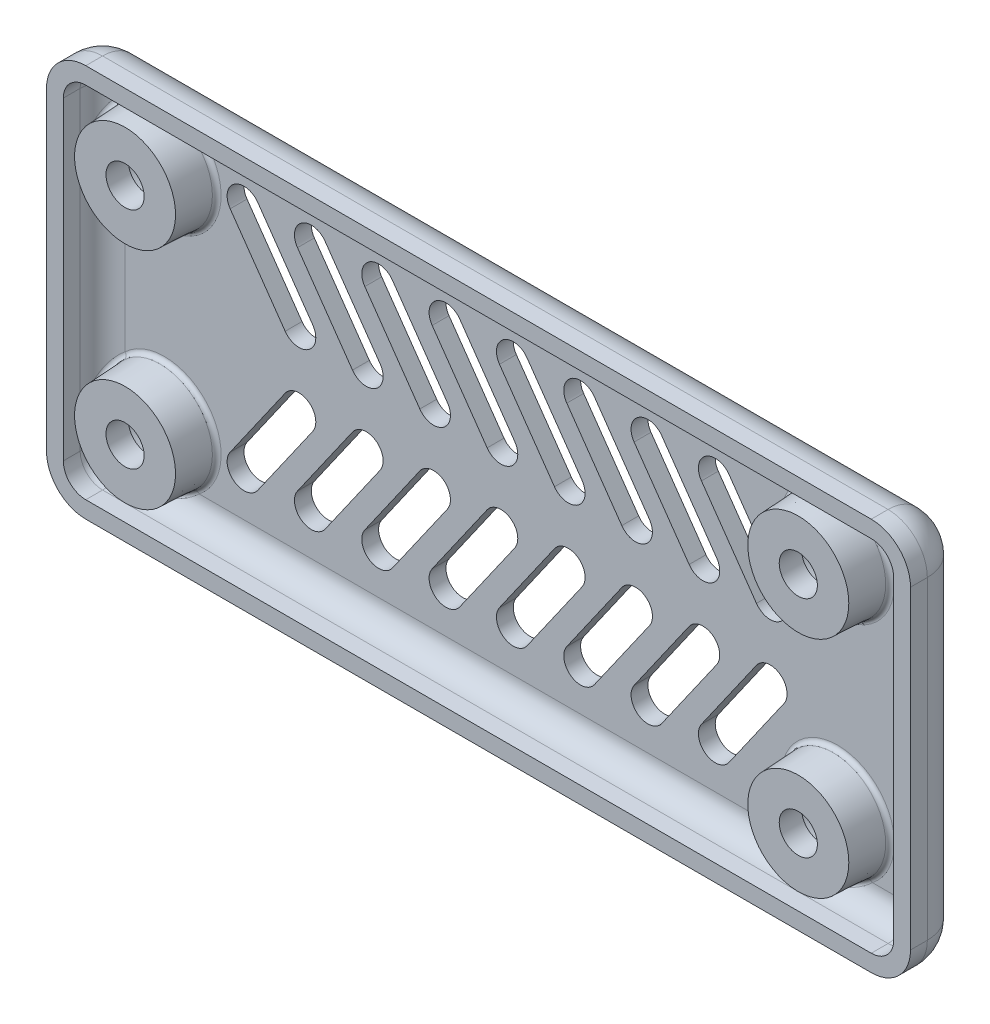
SolidWorks part; units mm, degrees
ref_plane "Płaszczyzna przednia" through (0, 0, 0) normal (0, 0, 1) x (1, 0, 0)
ref_plane "Płaszczyzna górna" through (0, 0, 0) normal (0, 1, 0) x (1, 0, 0)
ref_plane "Płaszczyzna prawa" through (0, 0, 0) normal (1, 0, 0) x (0, 0, -1)
sketch "Szkic1" plane through (0, 0, 0) normal (0, 0, 1) x (1, 0, 0)
  line L0 (0, 0) -> (1.5, 0) construction
  line L1 (-37, 17.5) -> (40, 17.5)
  line L2 (-37, 17.5) -> (-37, -17.5)
  line L3 (-37, -17.5) -> (40, -17.5)
  line L4 (40, 17.5) -> (40, -17.5)
  line L5 (-37, 17.5) -> (40, -17.5) construction
  line L6 (-37, -17.5) -> (40, 17.5) construction
  dimension "D1" = 37
  dimension "D2" = 35
  dimension "D3" = 40
extrude "Dodanie-wyciągnięcie1" add sketch "Szkic1" along normal blind 5
fillet "Zaokrąglenie1" radius 3.5 8 edges at (1.5, 17.5, 0) (-37, 0, 0) (1.5, -17.5, 0) (40, 0, 0) (-37, -17.5, 2.5) (40, -17.5, 2.5) (40, 17.5, 2.5) (-37, 17.5, 2.5)
shell "Skorupa1" thickness 1.5
ref_plane "Płaszczyzna1" through (0, 0, 5) normal (0, 0, 1) x (1, 0, 0)
sketch "Szkic2" plane through (0, 0, 5) normal (0, 0, 1) x (1, 0, 0)
  line L1 (-30, 10) -> (30, 10) construction
  line L2 (-30, 10) -> (-30, -10) construction
  line L3 (-30, -10) -> (30, -10) construction
  line L4 (30, 10) -> (30, -10) construction
  line L5 (-30, 10) -> (30, -10) construction
  line L6 (-30, -10) -> (30, 10) construction
  circle A0 centre (-30, 10) radius 2.5 construction
  circle A5 centre (30, 10) radius 2.5 construction
  circle A6 centre (30, 10) radius 4.5
  circle A7 centre (-30, 10) radius 4.5
  circle A8 centre (-30, -10) radius 2.5 construction
  circle A9 centre (30, -10) radius 2.5 construction
  circle A10 centre (-30, -10) radius 4.5
  circle A11 centre (30, -10) radius 4.5
  point P0 (0, 0)
  dimension "D3" = 5
  dimension "D4" = 2
  dimension "D1" = 20
  dimension "D2" = 60
extrude "Dodanie-wyciągnięcie2" add sketch "Szkic2" against normal up to surface (3.5 mm away) draft 3
fillet "Zaokrąglenie2" radius 0.4 12 edges at (30, -5.3166, 1.5) (29.5676, -14.6576, 1.6112) (30, 5.3166, 1.5) (30.4324, 14.6576, 1.6112) (-34.5958, -10.8079, 1.8269) (-26.4044, -6.9989, 1.5) (-33.0011, -13.5956, 1.5) (-30.4324, -14.6576, 1.6112) (-34.5958, 9.1921, 1.8269) (-26.4044, 6.9989, 1.5) (-33.0011, 13.5956, 1.5) (-29.5676, 14.6576, 1.6112)
hole_wizard "Pogłębienie walcowe pod M3 Śrubę z łbem stożkowym ściętym1" positions "Szkic 3D1" profile "Szkic3" counterbore size "M3" standard "ISO" end condition through all
sketch3d "Szkic 3D1"
  circle A0 centre (-30, -10, 5) radius 4.5 construction
  circle A1 centre (-30, 10, 5) radius 4.5 construction
  circle A2 centre (30, 10, 5) radius 4.5 construction
  circle A3 centre (30, -10, 5) radius 4.5 construction
  point P16 (-30, -10, 0)
  point P18 (30, -10, 0)
  point P20 (30, 10, 0)
  point P22 (-30, 10, 0)
  point P24 (0, 0, 0)
  point P27 (-30, -10, 9.5)
  point P30 (-30, 10, 9.5)
  point P31 (0, 0, 0)
  point P32 (0, 0, 0)
  point P35 (30, 10, 9.5)
  point P36 (0, 0, 0)
  point P39 (30, -10, 9.5)
  point P40 (0, 0, 0)
sketch "Szkic3" plane through (-30, -10, 0) normal (1, 0, 0) x (0, 1, 0)
  line L0 (0, 0) -> (0, 5)
  line L1 (0, 5) -> (1.7, 5)
  line L3 (1.7, 5) -> (1.7, 3)
  line L4 (1.7, 3) -> (3.5, 3)
  line L5 (3.5, 3) -> (3.5, 0)
  line L7 (3.5, 0) -> (0, 0)
  line L11 (0, -6.35) -> (0, 107.95) construction
  dimension "Średnica otworu na wylot" = 3.4
  dimension "Głębokość otworu na wylot" = 5
  dimension "Średnica pogłębienia walcowego" = 7
  dimension "Głębokość pogłębienia walcowego" = 3
sketch "Szkic4" plane through (-37, 0, 0) normal (-1, 0, 0) x (0, 0, 1)
  line L0 (5, 14) -> (5, -14) construction
  circle A0 centre (-3.7, -0.5) radius 5
  point P4 (0, 0)
  point P5 (0, 0)
  dimension "D1" = 10
  dimension "D2" = 8.7
  dimension "D3" = 0.5
extrude "Wytnij-wyciągnięcie1" [suppressed] cut sketch "Szkic4" against normal up to surface (1.5 mm away)
sketch "Szkic6" plane through (40, 0, 0) normal (1, 0, 0) x (0, 0, -1)
  line L0 (2, 0) -> (0, 0) construction
  line L1 (-5, -14) -> (-5, 14) construction
  circle A0 centre (2, 0) radius 4
  dimension "D1" = 8
  dimension "D2" = 7
extrude "Wytnij-wyciągnięcie2" [suppressed] cut sketch "Szkic6" against normal up to surface (1.5 mm away)
sketch "Szkic7" plane through (0, 0, 0) normal (0, 0, -1) x (-1, 0, 0)
  line L0 (0, 0) -> (-24, 0) construction
  line L1 (-24, 3.25) -> (-24, -3.25) construction
  line L2 (-24, 3.25) -> (-19.0985, 10.25) construction
  line L3 (-25.2287, 4.1104) -> (-20.3273, 11.1104)
  line L4 (-22.7713, 2.3896) -> (-17.8698, 9.3896)
  line L5 (-24, -3.25) -> (-19.0985, -10.25) construction
  line L6 (-22.7713, -2.3896) -> (-17.8698, -9.3896)
  line L7 (-25.2287, -4.1104) -> (-20.3273, -11.1104)
  line L8 (-16.7713, 2.3896) -> (-11.8698, 9.3896)
  line L9 (-19.2287, 4.1104) -> (-14.3273, 11.1104)
  line L10 (-19.2287, -4.1104) -> (-14.3273, -11.1104)
  line L11 (-16.7713, -2.3896) -> (-11.8698, -9.3896)
  line L12 (-18, 3.25) -> (-13.0985, 10.25) construction
  line L13 (-18, -3.25) -> (-13.0985, -10.25) construction
  line L14 (-10.7713, 2.3896) -> (-5.8698, 9.3896)
  line L15 (-13.2287, 4.1104) -> (-8.3273, 11.1104)
  line L16 (-13.2287, -4.1104) -> (-8.3273, -11.1104)
  line L17 (-10.7713, -2.3896) -> (-5.8698, -9.3896)
  line L18 (-12, 3.25) -> (-7.0985, 10.25) construction
  line L19 (-12, -3.25) -> (-7.0985, -10.25) construction
  line L20 (-4.7713, 2.3896) -> (0.1302, 9.3896)
  line L21 (-7.2287, 4.1104) -> (-2.3273, 11.1104)
  line L22 (-7.2287, -4.1104) -> (-2.3273, -11.1104)
  line L23 (-4.7713, -2.3896) -> (0.1302, -9.3896)
  line L24 (-6, 3.25) -> (-1.0985, 10.25) construction
  line L25 (-6, -3.25) -> (-1.0985, -10.25) construction
  line L26 (1.2287, 2.3896) -> (6.1302, 9.3896)
  line L27 (-1.2287, 4.1104) -> (3.6727, 11.1104)
  line L28 (-1.2287, -4.1104) -> (3.6727, -11.1104)
  line L29 (1.2287, -2.3896) -> (6.1302, -9.3896)
  line L30 (0, 3.25) -> (4.9015, 10.25) construction
  line L31 (0, -3.25) -> (4.9015, -10.25) construction
  line L32 (7.2287, 2.3896) -> (12.1302, 9.3896)
  line L33 (4.7713, 4.1104) -> (9.6727, 11.1104)
  line L34 (4.7713, -4.1104) -> (9.6727, -11.1104)
  line L35 (7.2287, -2.3896) -> (12.1302, -9.3896)
  line L36 (6, 3.25) -> (10.9015, 10.25) construction
  line L37 (6, -3.25) -> (10.9015, -10.25) construction
  line L38 (13.2287, 2.3896) -> (18.1302, 9.3896)
  line L39 (10.7713, 4.1104) -> (15.6727, 11.1104)
  line L40 (10.7713, -4.1104) -> (15.6727, -11.1104)
  line L41 (13.2287, -2.3896) -> (18.1302, -9.3896)
  line L42 (12, 3.25) -> (16.9015, 10.25) construction
  line L43 (12, -3.25) -> (16.9015, -10.25) construction
  line L44 (19.2287, 2.3896) -> (24.1302, 9.3896)
  line L45 (16.7713, 4.1104) -> (21.6727, 11.1104)
  line L46 (16.7713, -4.1104) -> (21.6727, -11.1104)
  line L47 (19.2287, -2.3896) -> (24.1302, -9.3896)
  line L48 (18, 3.25) -> (22.9015, 10.25) construction
  line L49 (18, -3.25) -> (22.9015, -10.25) construction
  line L50 (-22.7713, 2.3896) -> (-16.7713, 2.3896) construction
  arc A0 (-25.2287, 4.1104) -> (-22.7713, 2.3896) centre (-24, 3.25) ccw
  arc A1 (-17.8698, 9.3896) -> (-20.3273, 11.1104) centre (-19.0985, 10.25) ccw
  arc A2 (-22.7713, -2.3896) -> (-25.2287, -4.1104) centre (-24, -3.25) ccw
  arc A3 (-20.3273, -11.1104) -> (-17.8698, -9.3896) centre (-19.0985, -10.25) ccw
  arc A4 (-19.2287, 4.1104) -> (-16.7713, 2.3896) centre (-18, 3.25) ccw
  arc A5 (-11.8698, 9.3896) -> (-14.3273, 11.1104) centre (-13.0985, 10.25) ccw
  arc A6 (-16.7713, -2.3896) -> (-19.2287, -4.1104) centre (-18, -3.25) ccw
  arc A7 (-14.3273, -11.1104) -> (-11.8698, -9.3896) centre (-13.0985, -10.25) ccw
  arc A8 (-13.2287, 4.1104) -> (-10.7713, 2.3896) centre (-12, 3.25) ccw
  arc A9 (-5.8698, 9.3896) -> (-8.3273, 11.1104) centre (-7.0985, 10.25) ccw
  arc A10 (-10.7713, -2.3896) -> (-13.2287, -4.1104) centre (-12, -3.25) ccw
  arc A11 (-8.3273, -11.1104) -> (-5.8698, -9.3896) centre (-7.0985, -10.25) ccw
  arc A12 (-7.2287, 4.1104) -> (-4.7713, 2.3896) centre (-6, 3.25) ccw
  arc A13 (0.1302, 9.3896) -> (-2.3273, 11.1104) centre (-1.0985, 10.25) ccw
  arc A14 (-4.7713, -2.3896) -> (-7.2287, -4.1104) centre (-6, -3.25) ccw
  arc A15 (-2.3273, -11.1104) -> (0.1302, -9.3896) centre (-1.0985, -10.25) ccw
  arc A16 (-1.2287, 4.1104) -> (1.2287, 2.3896) centre (0, 3.25) ccw
  arc A17 (6.1302, 9.3896) -> (3.6727, 11.1104) centre (4.9015, 10.25) ccw
  arc A18 (1.2287, -2.3896) -> (-1.2287, -4.1104) centre (0, -3.25) ccw
  arc A19 (3.6727, -11.1104) -> (6.1302, -9.3896) centre (4.9015, -10.25) ccw
  arc A20 (4.7713, 4.1104) -> (7.2287, 2.3896) centre (6, 3.25) ccw
  arc A21 (12.1302, 9.3896) -> (9.6727, 11.1104) centre (10.9015, 10.25) ccw
  arc A22 (7.2287, -2.3896) -> (4.7713, -4.1104) centre (6, -3.25) ccw
  arc A23 (9.6727, -11.1104) -> (12.1302, -9.3896) centre (10.9015, -10.25) ccw
  arc A24 (10.7713, 4.1104) -> (13.2287, 2.3896) centre (12, 3.25) ccw
  arc A25 (18.1302, 9.3896) -> (15.6727, 11.1104) centre (16.9015, 10.25) ccw
  arc A26 (13.2287, -2.3896) -> (10.7713, -4.1104) centre (12, -3.25) ccw
  arc A27 (15.6727, -11.1104) -> (18.1302, -9.3896) centre (16.9015, -10.25) ccw
  arc A28 (16.7713, 4.1104) -> (19.2287, 2.3896) centre (18, 3.25) ccw
  arc A29 (24.1302, 9.3896) -> (21.6727, 11.1104) centre (22.9015, 10.25) ccw
  arc A30 (19.2287, -2.3896) -> (16.7713, -4.1104) centre (18, -3.25) ccw
  arc A31 (21.6727, -11.1104) -> (24.1302, -9.3896) centre (22.9015, -10.25) ccw
  point P3 (-21.5493, 6.75)
  point P6 (-24, 0)
  point P13 (-21.5493, -6.75)
  point P18 (-15.5493, 6.75)
  point P28 (-15.5493, -6.75)
  point P33 (-9.5493, 6.75)
  point P42 (-9.5493, -6.75)
  point P47 (-3.5493, 6.75)
  point P56 (-3.5493, -6.75)
  point P61 (2.4507, 6.75)
  point P70 (2.4507, -6.75)
  point P75 (8.4507, 6.75)
  point P84 (8.4507, -6.75)
  point P89 (14.4507, 6.75)
  point P98 (14.4507, -6.75)
  point P103 (20.4507, 6.75)
  point P112 (20.4507, -6.75)
  dimension "D1" = 6.5
  dimension "D2" = 24
  dimension "D3" = 3
  dimension "D4" = 7
  dimension "D5" = 35
  dimension "D6" = 35
  dimension "D8" = 6
  dimension "D7" = 8
extrude "Wytnij-wyciągnięcie3" cut sketch "Szkic7" against normal up to surface (1.5 mm away) up to face at (8.0273, 0, 1.5)
equation "\"A\"=0.4"
equation "\"D6@Szkic7\"=\"D5@Szkic7\""
